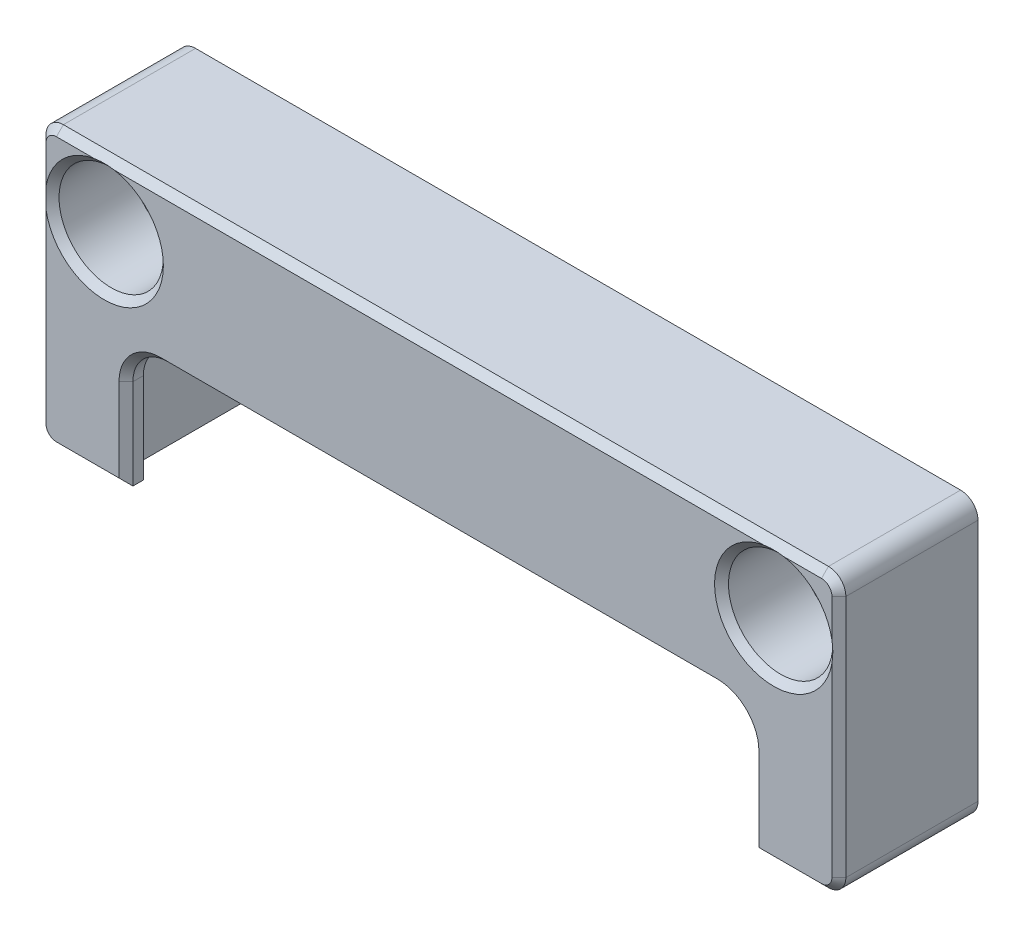
SolidWorks part; units mm, degrees
ref_plane "Front Plane" through (0, 0, 0) normal (0, 0, 1) x (1, 0, 0)
ref_plane "Top Plane" through (0, 0, 0) normal (0, 1, 0) x (1, 0, 0)
ref_plane "Right Plane" through (0, 0, 0) normal (1, 0, 0) x (0, 0, -1)
sketch "Sketch1" plane through (0, 0, 0) normal (0, 0, 1) x (1, 0, 0)
  line L0 (0, 0) -> (0, 16)
  line L1 (0, 16) -> (46, 16)
  line L2 (46, 16) -> (46, 0)
  line L3 (46, 0) -> (41, 0)
  line L4 (41, 0) -> (41, 5.2)
  line L5 (39, 7.2) -> (7, 7.2)
  line L6 (5, 5.2) -> (5, 0)
  line L7 (5, 0) -> (0, 0)
  arc A0 (41, 5.2) -> (39, 7.2) centre (39, 5.2) ccw
  arc A1 (7, 7.2) -> (5, 5.2) centre (7, 5.2) ccw
  dimension "D1" = 2
  dimension "D2" = 7.2
  dimension "D3" = 46
  dimension "D4" = 36
  dimension "D5" = 16
extrude "Boss-Extrude1" add sketch "Sketch1" along normal blind 8
sketch "Sketch2" plane through (0, 0, 8) normal (0, 0, 1) x (1, 0, 0)
  line L0 (0, 12.25) -> (3.75, 12.25) construction
  line L1 (0, 16) -> (0, 0) construction
  line L2 (3.75, 12.25) -> (42.25, 12.25) construction
  line L3 (42.25, 12.25) -> (46, 12.25) construction
  line L4 (46, 0) -> (46, 16) construction
  line L5 (46, 16) -> (0, 16) construction
  circle A0 centre (3.75, 12.25) radius 1.65
  circle A1 centre (42.25, 12.25) radius 1.65
  dimension "D1" = 38.5
  dimension "D2" = 3.3
  dimension "D3" = 3.75
extrude "Cut-Extrude1" cut sketch "Sketch2" against normal up to next
sketch "Sketch3" plane through (0, 0, 8) normal (0, 0, 1) x (1, 0, 0)
  circle A0 centre (3.75, 12.25) radius 3
  circle A1 centre (42.25, 12.25) radius 3
  dimension "D1" = 6
extrude "Cut-Extrude2" cut sketch "Sketch3" against normal blind 4.5
chamfer "Chamfer1" [suppressed] distance 1.35 angle 45
sketch "Sketch4" plane through (0, 0, 0) normal (0, 0, -1) x (-1, 0, 0)
  line L0 (-4, 0) -> (-5, 0)
  line L1 (0, 0) -> (-5, 0) construction
  line L2 (-5, 0) -> (-5, 5.2)
  line L3 (-7, 7.2) -> (-39, 7.2)
  line L4 (-41, 5.2) -> (-41, 0)
  line L5 (-41, 0) -> (-42, 0)
  line L6 (-41, 0) -> (-46, 0) construction
  line L7 (-42, 0) -> (-42, 5.2)
  line L8 (-39, 8.2) -> (-7, 8.2)
  line L9 (-4, 5.2) -> (-4, 0)
  arc A0 (-5, 5.2) -> (-7, 7.2) centre (-7, 5.2) ccw
  arc A1 (-39, 7.2) -> (-41, 5.2) centre (-39, 5.2) ccw
  arc A2 (-42, 5.2) -> (-39, 8.2) centre (-39, 5.2) cw
  arc A3 (-7, 8.2) -> (-4, 5.2) centre (-7, 5.2) cw
  dimension "D1" = 38
extrude "Cut-Extrude3" cut sketch "Sketch4" against normal offset from surface (7 mm away) 1 up to face at (6.75, 12.25, 8)
fillet "Fillet1" radius 1 4 edges at (0, 16, 4) (46, 16, 4) (46, 0, 4) (0, 0, 4)
chamfer "Chamfer2" distance 0.4 angle 45 16 edges at (45.7071, 15.7071, 8) (46, 8, 8) (45.7071, 0.2929, 8) (43, 0, 8) (41, 2.6, 8) (40.4142, 6.6142, 8) (23, 7.2, 8) (5.5858, 6.6142, 8) (5, 2.6, 8) (3, 0, 8) (0.2929, 0.2929, 8) (0, 8, 8) (0.2929, 15.7071, 8) (23, 16, 8) (45.25, 12.25, 8) (6.75, 12.25, 8)
